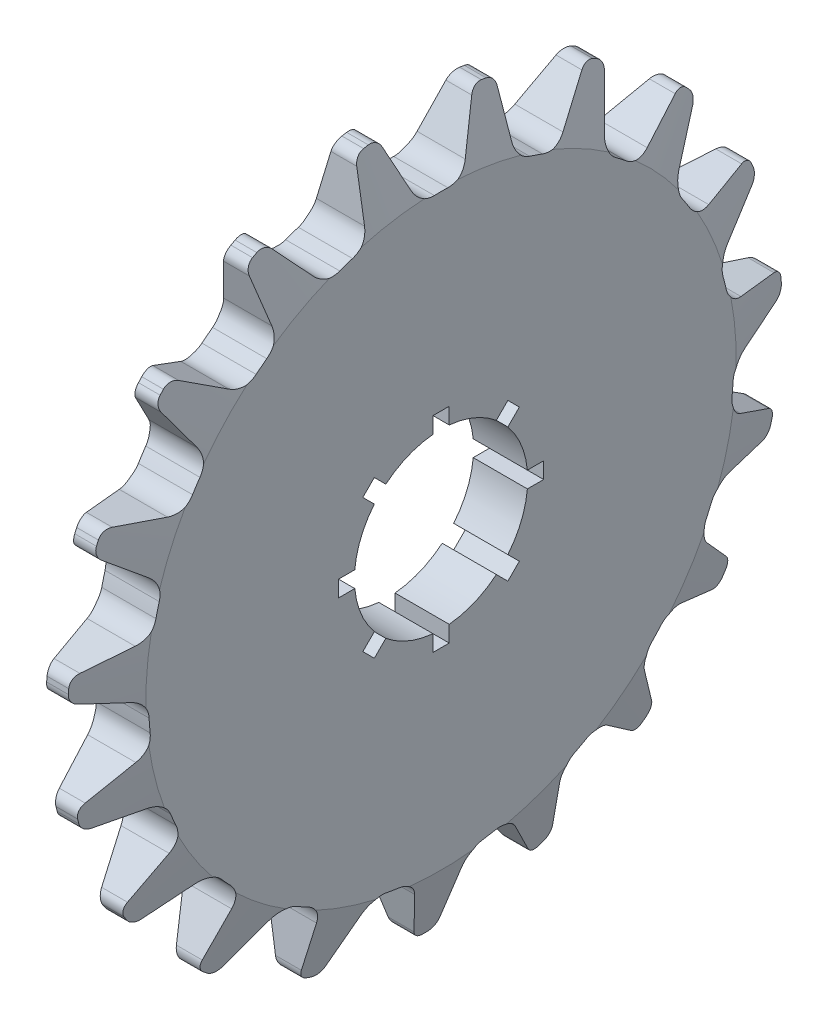
SolidWorks part; units mm, degrees
material "AISI 4140 Steel, quenched & tempered"
ref_plane "Front Plane" through (0, 0, 0) normal (1, 0, 0) x (0, 1, 0)
ref_plane "Top Plane" through (0, 0, 0) normal (0, 0, 1) x (0, 1, 0)
ref_plane "Right Plane" through (0, 0, 0) normal (0, 1, 0) x (-1, 0, 0)
sketch "Sketch1" plane through (0, 0, 0) normal (1, 0, 0) x (0, 1, 0)
  circle A0 centre (0, 0) radius 27
  circle A1 centre (0, 0) radius 22
  circle A2 centre (0, 0) radius 12
  circle A3 centre (0, 0) radius 8
  dimension "D1" = 24
  dimension "D2" = 44
  dimension "D3" = 54
  dimension "D4" = 16
extrude "Boss-Extrude1" add sketch "Sketch1" along normal mid plane 5 contours A0 A1 | A1 A2 | A2 A3 region at (0, -26.2363, 0) region at (0, -21.3777, 0) region at (0, -11.6606, 0)
sketch "Sketch2" plane through (2.5, 0, 0) normal (1, 0, 0) x (0, 1, 0)
  line L0 (0, 0) -> (-50.1268, 0) construction
  line L1 (-33, 1) -> (-33, -1)
  line L2 (-33, -1) -> (-26.884, -2.5)
  line L3 (-33, 1) -> (-26.884, 2.5)
  circle A0 centre (0, 0) radius 27 construction
  circle A1 centre (0, 0) radius 27
  arc A2 (-32.9847, 1.0037) -> (-32.9847, -1.0037) centre (0, 0) ccw
  circle A4 centre (0, 0) radius 33 construction
  point P8 (-33, 0)
  point P10 (31.5581, 9.6483)
  circle M6 centre (0, 0) radius 27
  dimension "D3" = 5
  dimension "D2" = 2
  dimension "D1" = 6
extrude "Boss-Extrude2" add sketch "Sketch2" against normal up to surface (5 mm away) contours L3 A2 L2 M6 region at (2.5, -29.5509, 0) up to face at (-2.5, 0, -27)
fillet "Fillet1" radius 1 2 edges at (0, -32.9847, -1.0037) (0, -32.9847, 1.0037)
fillet "Fillet2" radius 2 2 edges at (0, -26.884, -2.5) (0, -26.884, 2.5)
pattern_circular "CirPattern1" count 19 over 360 about axis through (2.5, 0, 0) along (1, 0, 0) of "Fillet1", "Boss-Extrude2", "Fillet2"
sketch "Sketch7" plane through (2.5, 0, 0) normal (1, 0, 0) x (0, 1, 0)
  line L2 (-36.3144, 0) -> (37.4583, 0) construction
  circle A1 centre (0, 0) radius 33
  dimension "D1" = 66
ref_plane "Plane1" through (0, 0, 0) normal (0, 0, -1) x (0, 1, 0)
sketch "Sketch3" plane through (0, 0, 0) normal (0, 0, 1) x (-1, 0, 0)
  line L3 (-14.363, 0) -> (11.8314, 0) construction
  line L4 (0, 37.2459) -> (0, -38.8612) construction
  line L6 (1, 33) -> (2.5, 33)
  line L8 (-2.5, 36.3144) -> (-2.5, -37.4583) construction
  line L9 (-2.5, 33) -> (-2.5, 27.2414)
  line L12 (1, 33) -> (2.5, 27.2414)
  line L13 (2.5, 33) -> (-2.5, 33)
  line L14 (-1, 33) -> (-0.4452, 35.1298)
  line L15 (-1, 33) -> (-2.5, 33)
  line L16 (2.5, 33) -> (2.5, 27.2414)
  line L17 (-2.5, 33) -> (-1, 33)
  line L18 (-2.5, 27.2414) -> (-2.5, 33)
  line L20 (-1, 33) -> (-2.5, 27.2414)
  dimension "D1" = 75.4
  dimension "D3" = 1
revolve "Cut-Revolve1" cut sketch "Sketch3" angle 360 about L3 region at (-2, -31.0805, 0) region at (2, -31.0805, 0)
sketch "Sketch4" plane through (-2.5, 0, 0) normal (-1, 0, 0) x (0, -1, 0)
  line L0 (0, 0) -> (0, 11.0202) construction
  line L2 (-0.75, 9.4648) -> (0.75, 9.4648)
  line L3 (-0.75, 9.4648) -> (-0.75, 7.9648)
  line L4 (-0.75, 7.9648) -> (0.75, 7.9648)
  line L5 (0.75, 9.4648) -> (0.75, 7.9648)
  circle A0 centre (0, 0) radius 8 construction
  circle A1 centre (0, 0) radius 8
  point P8 (0, 9.4648)
  dimension "D1" = 1.5
  dimension "D2" = 1.5
extrude "Cut-Extrude1" cut sketch "Sketch4" against normal through all both and the other way through all contours A1 L0 L2 L3 | L0 A1 L5 L2 region at (-2.5, 0.3765, 8.7265) region at (-2.5, -0.3765, 8.7265)
pattern_circular "CirPattern2" count 8 over 360 about axis through (-2.5, 0, 0) along (1, 0, 0) of "Cut-Extrude1"
extrude "Boss-Extrude3" add sketch "Sketch1<3>" against normal blind 3.5 contours A1 A2 region at (0, -21.3777, 0)
sketch "Sketch1<3>" plane through (0, 0, 0) normal (1, 0, 0) x (0, 1, 0) same geometry as "Sketch1"
sketch "Sketch6" plane through (-3.5, 0, 0) normal (-1, 0, 0) x (0, -1, 0)
  line L0 (0, 0) -> (0, 33.6066) construction
  line L1 (0, 14) -> (2.5981, 15.5)
  line L2 (2.5981, 15.5) -> (2.5981, 18.5)
  line L3 (2.5981, 18.5) -> (0, 20)
  line L4 (0, 20) -> (-2.5981, 18.5)
  line L5 (-2.5981, 18.5) -> (-2.5981, 15.5)
  line L6 (-2.5981, 15.5) -> (0, 14)
  circle A0 centre (0, 17) radius 2.5981 construction
  circle A5 centre (0, 0) radius 17
  circle A6 centre (0, 0) radius 17
  dimension "D1" = 5
  dimension "D2" = 3
extrude "Boss-Extrude4" add sketch "Sketch6" along normal blind 2 contours A6 L2 L3 L4 L5 | L2 A6 L5 L6 L1 region at (-3.5, 0, 15.7997) region at (-3.5, 0, 18.1315)
pattern_circular "CirPattern3" count 3 over 360 about axis through (-3.5, 0, 0) along (1, 0, 0) of "Boss-Extrude4"
